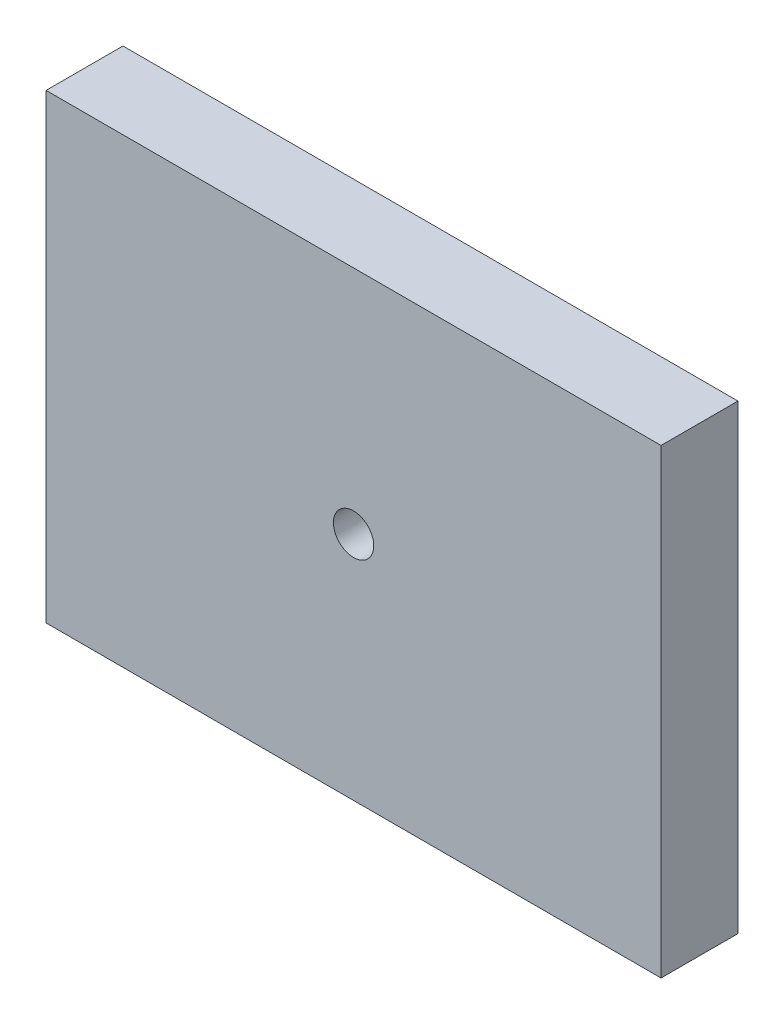
SolidWorks part; units mm, degrees
ref_plane "Plan de face" through (0, 0, 0) normal (0, 0, 1) x (1, 0, 0)
ref_plane "Plan de dessus" through (0, 0, 0) normal (0, 1, 0) x (1, 0, 0)
ref_plane "Plan de droite" through (0, 0, 0) normal (1, 0, 0) x (0, 0, -1)
sketch "Esquisse1" plane through (0, 0, 0) normal (0, 0, 1) x (1, 0, 0)
  line L1 (-50.8, -38.1) -> (50.8, -38.1)
  line L2 (-50.8, -38.1) -> (-50.8, 38.1)
  line L3 (-50.8, 38.1) -> (50.8, 38.1)
  line L4 (50.8, -38.1) -> (50.8, 38.1)
  line L5 (-50.8, -38.1) -> (50.8, 38.1) construction
  line L6 (-50.8, 38.1) -> (50.8, -38.1) construction
  point P0 (0, 0)
  dimension "D1" = 101.6
  dimension "D2" = 76.2
extrude "Boss.-Extru.1" add sketch "Esquisse1" along normal blind 12.7
sketch "Esquisse2" plane through (0, 0, 0) normal (0, 0, -1) x (-1, 0, 0)
  line L0 (-50.8, 38.1) -> (0, 38.1) construction
  line L1 (-50.8, 38.1) -> (50.8, 38.1) construction
  line L2 (0, 38.1) -> (0, 0) construction
  circle A0 centre (0, 0) radius 3.3337
  dimension "D1" = 6.6675
extrude "Enlèv. mat.-Extru.1" cut sketch "Esquisse2" against normal through all
